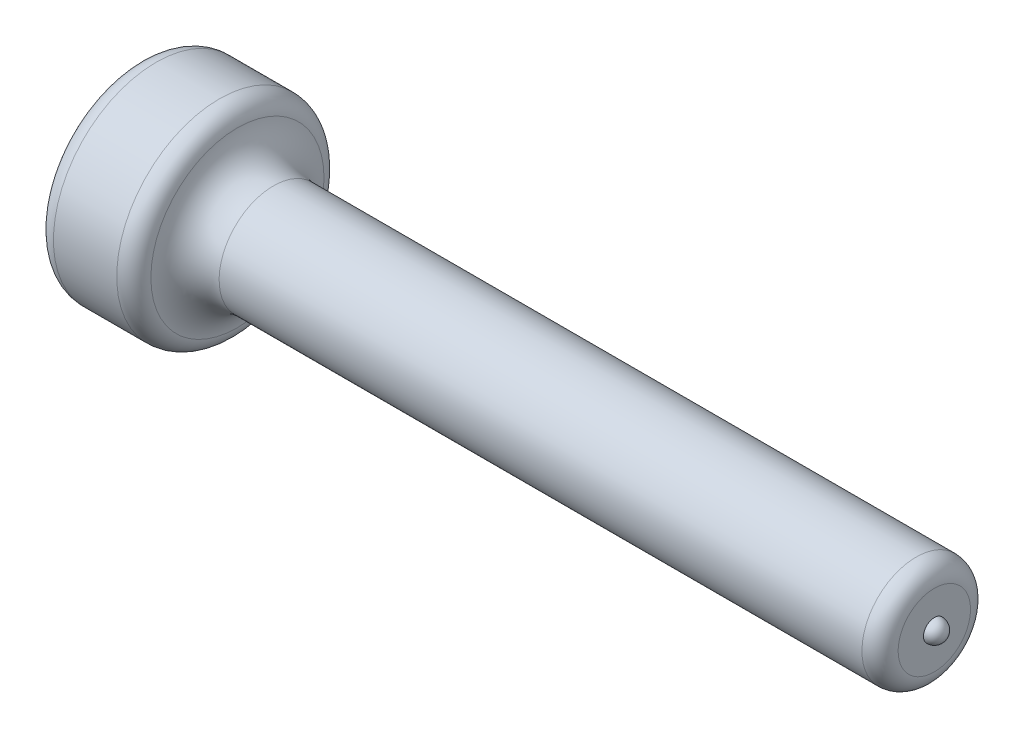
SolidWorks part; units mm, degrees
ref_plane "Front" through (0, 0, 0) normal (0, 0, 1) x (1, 0, 0)
ref_plane "Top" through (0, 0, 0) normal (0, 1, 0) x (1, 0, 0)
ref_plane "Right" through (0, 0, 0) normal (1, 0, 0) x (0, 0, -1)
sketch "Sketch1" plane through (26.6046, 20.9296, 0) normal (0, 0, 1) x (0, 1, 0)
  line L0 (-20.9296, -17.3954) -> (-17.9296, -17.3954)
  line L1 (-17.9296, -17.3954) -> (-17.9296, 21.1246)
  line L2 (-17.9296, 21.1246) -> (-15.2546, 21.1246)
  line L3 (-15.2546, 21.1246) -> (-15.2546, 26.6046)
  line L4 (-15.2546, 26.6046) -> (-20.9296, 26.6046)
  line L5 (-20.9296, 26.6046) -> (-20.9296, -17.3954)
  line L6 (-20.9296, 63.1371) -> (-20.9296, -15.6029) construction
revolve "Base-Revolve" add sketch "Sketch1" angle 360 about L6
fillet "Fillet1" radius 2 1 edges at (5.48, -3, 0)
fillet "Fillet2" radius 1 1 edges at (44, -3, 0)
fillet "Fillet3" radius 1 2 edges at (5.48, -5.675, 0) (0, -5.675, 0)
sketch "Sketch2" plane through (0, 0, 0) normal (0, 0, 1) x (1, 0, 0)
  line L0 (0, 0) -> (45.2246, 0) construction
  line L1 (44, -2) -> (44, 2) construction
  line L2 (43.4, 0) -> (44.6, 0)
  arc A0 (44.6, 0) -> (43.4, 0) centre (44, 0) ccw
  dimension "D1" = 0.6
revolve "Revolve1" add sketch "Sketch2" angle 360 about L0
sketch "Sketch3" plane through (0, 0, 0) normal (0, 0, 1) x (1, 0, 0)
  line L0 (0, 4.675) -> (0, -4.675) construction
  line L1 (0, 0) -> (1.096, 0)
  line L2 (0, 0) -> (0, 3.7833)
  line L3 (0, 3.7833) -> (1.096, 3.7833)
  line L4 (1.096, 0) -> (1.096, 3.7833)
  line L5 (0, 0) -> (-2.8633, 0) construction
  dimension "D1" = 1.096
  dimension "D2" = 7.5667
revolve "Cut-Revolve1" cut sketch "Sketch3" angle 360 about L5
equation "\"D1@Fillet2\"=\"r@Fillet1\"/2"
equation "\"D1@Fillet3\"=\"r@Fillet1\" / 2"
equation "\"D1@Sketch2\" = \"d@Sketch1\" / 10"
equation "\"D1@Sketch3\" = \"K@Sketch1\" / 5"
equation "\"D2@Sketch3\" = \"dk@Sketch1\" *2 /3"
